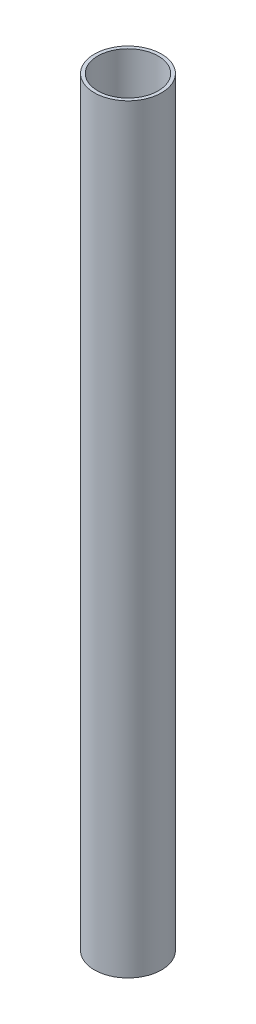
SolidWorks part; units mm, degrees
material "Toray T700"
ref_plane "Front" through (0, 0, 0) normal (0, 0, 1) x (1, 0, 0)
ref_plane "Top" through (0, 0, 0) normal (0, 1, 0) x (1, 0, 0)
ref_plane "Right" through (0, 0, 0) normal (1, 0, 0) x (0, 0, -1)
sketch "Sketch1" plane through (0, 0, 0) normal (0, 1, 0) x (1, 0, 0)
  line L5 (4.7969, 0) -> (-5.97, 0) construction
  circle A0 centre (0, 0) radius 10
  circle A1 centre (0, 0) radius 9
  dimension "D1" = 20
  dimension "D2" = 18
extrude "Boss-Extrude1" add sketch "Sketch1" along normal blind 226.2
